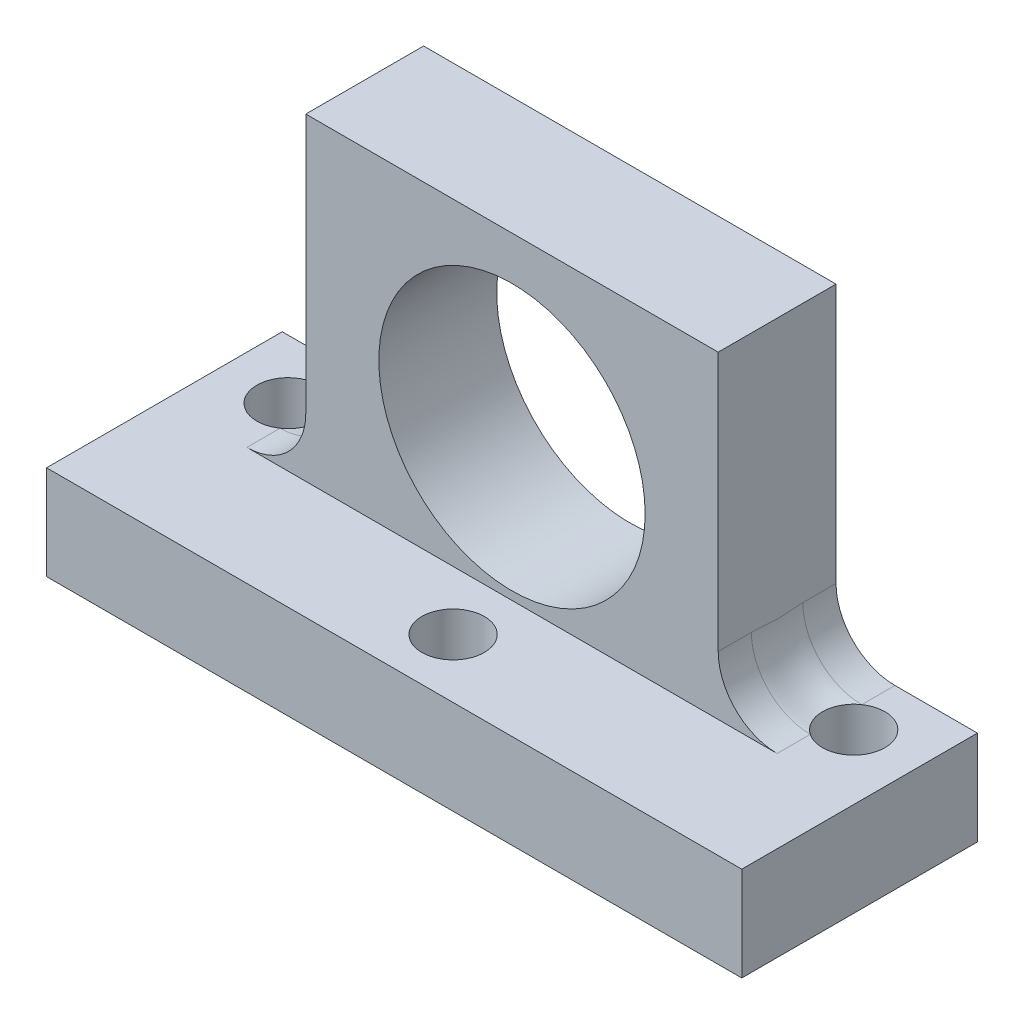
SolidWorks part; units mm, degrees
ref_plane "Спереди" through (0, 0, 0) normal (0, 0, 1) x (1, 0, 0)
ref_plane "Сверху" through (0, 0, 0) normal (0, 1, 0) x (1, 0, 0)
ref_plane "Справа" through (0, 0, 0) normal (1, 0, 0) x (0, 0, -1)
sketch "Эскиз1" plane through (0, 0, 0) normal (0, 0, 1) x (1, 0, 0)
  line L1 (0, 0) -> (-35, 0)
  line L2 (0, 0) -> (0, 35)
  line L3 (0, 35) -> (-35, 35)
  line L4 (-35, 0) -> (-35, 35)
  line L5 (0, 0) -> (12, 0)
  line L6 (0, 0) -> (0, 8)
  line L7 (0, 8) -> (12, 8)
  line L8 (12, 0) -> (12, 8)
  line L9 (-35, 0) -> (-47, 0)
  line L10 (-35, 0) -> (-35, 8)
  line L11 (-35, 8) -> (-47, 8)
  line L12 (-47, 0) -> (-47, 8)
  circle A0 centre (-17.5, 20) radius 11.3
  dimension "D7" = 22.6
  dimension "D1" = 35
  dimension "D2" = 12
  dimension "D3" = 12
  dimension "D4" = 35
  dimension "D5" = 8
  dimension "D6" = 8
  dimension "D8" = 20
  dimension "D9" = 17.5
extrude "Бобышка-Вытянуть1" add sketch "Эскиз1" along normal blind 10 contours L4 L1 L2 L3 A0 | L12 L9 L4 L11 | L5 L8 L7 L2 region at (-17.5, 0.495, 0) region at (6, 4, 0) region at (-41, 4, 0)
sketch "Эскиз2" plane through (0, 8, 0) normal (0, 1, 0) x (1, 0, 0)
  line L0 (-35, -10) -> (-35, 0) construction
  line L1 (-35, -10) -> (-47, -10) construction
  circle A0 centre (-41.5, -5) radius 2.65
  dimension "D1" = 5.3
  dimension "D2" = 6.5
  dimension "D3" = 5
extrude "Вырез-Вытянуть1" cut sketch "Эскиз2" against normal blind 10 contours A0
sketch "Эскиз3" plane through (0, 8, 0) normal (0, 1, 0) x (1, 0, 0)
  line L0 (0, -10) -> (0, 0) construction
  line L1 (0, -10) -> (12, -10) construction
  circle A0 centre (6.5, -5) radius 2.65
  point P4 (0, 0)
  dimension "D1" = 5.3
  dimension "D2" = 6.5
  dimension "D3" = 5
extrude "Вырез-Вытянуть2" cut sketch "Эскиз3" against normal blind 10
fillet "Скругление2" radius 5 2 edges at (0, 8, 5) (-35, 8, 5)
sketch "Эскиз4" plane through (0, 0, 10) normal (0, 0, 1) x (1, 0, 0)
  line L1 (-47, 0) -> (12, 0)
  line L2 (-47, 0) -> (-47, 8)
  line L3 (-47, 8) -> (12, 8)
  line L4 (12, 0) -> (12, 8)
extrude "Бобышка-Вытянуть2" add sketch "Эскиз4" along normal blind 10
ref_plane "Плоскость4" through (5, 8, 10) normal (-1, 0, 0) x (0, 0, 1)
sketch "Эскиз6" plane through (0, 8, 0) normal (0, 1, 0) x (1, 0, 0)
  line L0 (5, -10) -> (-40, -10) construction
  line L1 (-47, -20) -> (-47, 0) construction
  circle A0 centre (-17.5, -15) radius 2.65
  point P4 (0, 0)
  dimension "D1" = 5.3
  dimension "D2" = 5
  dimension "D3" = 29.5
extrude "Вырез-Вытянуть3" cut sketch "Эскиз6" against normal blind 10
